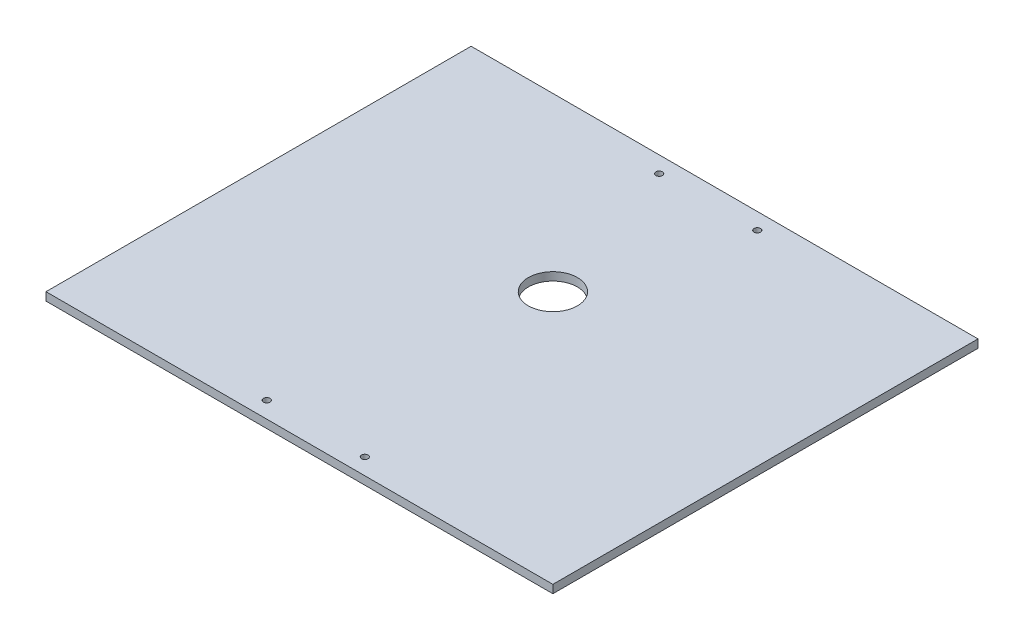
SolidWorks part; units mm, degrees
ref_plane "前视基准面" through (0, 0, 0) normal (0, 0, 1) x (1, 0, 0)
ref_plane "上视基准面" through (0, 0, 0) normal (0, 1, 0) x (1, 0, 0)
ref_plane "右视基准面" through (0, 0, 0) normal (1, 0, 0) x (0, 0, -1)
sketch "Sketch2" plane through (0, 0, 0) normal (0, 1, 0) x (1, 0, 0)
  line L1 (-60, 130) -> (60, 130)
  line L2 (-60, 130) -> (-60, -130)
  line L3 (-60, -130) -> (60, -130)
  line L4 (60, 130) -> (60, -130)
  line L5 (-60, 130) -> (60, -130) construction
  line L6 (-60, -130) -> (60, 130) construction
  point P0 (0, 0)
  dimension "D1" = 120
  dimension "D2" = 260
extrude "Boss-Extrude1" add sketch "Sketch2" along normal blind 5
sketch "Sketch3" plane through (0, 5, 0) normal (0, 1, 0) x (1, 0, 0)
  line L0 (60, -130) -> (60, 130) construction
  line L1 (-60, -130) -> (60, -130) construction
  circle A0 centre (0, 25) radius 15
  dimension "D1" = 30
  dimension "D3" = 155
  dimension "D2" = 60
extrude "Cut-Extrude1" cut sketch "Sketch3" against normal through all
sketch "Sketch5" plane through (0, 5, 0) normal (0, 1, 0) x (1, 0, 0)
  line L0 (-60, 0) -> (60, 0) construction
  line L1 (-60, 130) -> (-60, -130) construction
  line L2 (60, -130) -> (60, 130) construction
  line L3 (-60, 120) -> (60, 120) construction
  line L4 (60, 130) -> (-60, 130) construction
  line L5 (0, 0) -> (0, 130) construction
  circle A0 centre (-30, 120) radius 2
  circle A1 centre (30, 120) radius 2
  circle A2 centre (30, -120) radius 2
  circle A3 centre (-30, -120) radius 2
  dimension "D2" = 30
  dimension "D3" = 4
  dimension "D1" = 10
extrude "Cut-Extrude2" cut sketch "Sketch5" against normal through all
sketch "Sketch6" plane through (0, 5, 0) normal (0, 1, 0) x (1, 0, 0)
  line L0 (-60, -130) -> (60, -130) construction
  line L1 (60, 130) -> (155, 130)
  line L2 (60, 130) -> (60, -130)
  line L3 (60, -130) -> (155, -130)
  line L4 (155, 130) -> (155, -130)
  line L5 (0, 0) -> (0, 130) construction
  line L6 (60, 130) -> (-60, 130) construction
  line L7 (-155, 130) -> (-155, -130)
  line L8 (-60, -130) -> (-155, -130)
  line L9 (-60, 130) -> (-60, -130)
  line L10 (-60, 130) -> (-155, 130)
  dimension "D1" = 95
extrude "Boss-Extrude2" add sketch "Sketch6" against normal blind 5
